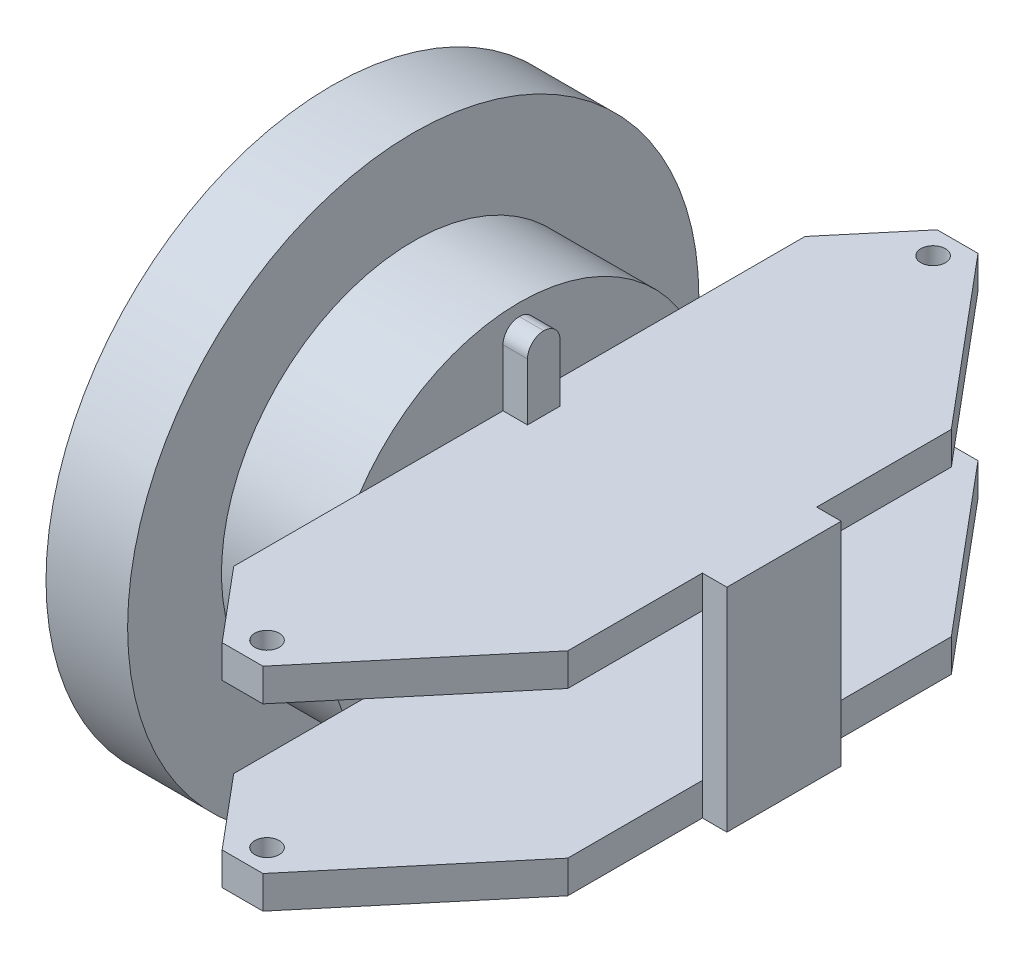
SolidWorks part; units mm, degrees
ref_plane "Front Plane" through (0, 0, 0) normal (0, 0, 1) x (1, 0, 0)
ref_plane "Top Plane" through (0, 0, 0) normal (0, 1, 0) x (1, 0, 0)
ref_plane "Right Plane" through (0, 0, 0) normal (1, 0, 0) x (0, 0, -1)
sketch "Sketch1" plane through (0, 0, 0) normal (1, 0, 0) x (0, 0, -1)
  circle A0 centre (0, 0) radius 35
  dimension "D1" = 70
extrude "Boss-Extrude1" add sketch "Sketch1" along normal blind 10
sketch "Sketch2" plane through (10, 0, 0) normal (1, 0, 0) x (0, 0, -1)
  circle A0 centre (0, 0) radius 23.5
  dimension "D1" = 47
extrude "Boss-Extrude2" add sketch "Sketch2" along normal blind 13
ref_plane "Plane1" through (0, 13, 0) normal (0, 1, 0) x (1, 0, 0)
sketch "Sketch3" plane through (0, 13, 0) normal (0, 1, 0) x (1, 0, 0)
  line L1 (23, 0) -> (23, -35)
  line L2 (23, -23.5) -> (23, 23.5) construction
  dimension "D1" = 35
sketch "Sketch5" plane through (0, 13, 0) normal (0, 1, 0) x (1, 0, 0)
  line L0 (23, 35) -> (23, -35)
  line L1 (23, -23.5) -> (23, 23.5) construction
  line L2 (23, -35) -> (30.3921, -43.8095)
  line L3 (30.3921, -43.8095) -> (35.3921, -43.8095)
  line L4 (35.3921, -43.8095) -> (52.4338, -23.5)
  line L5 (35.3921, -43.8095) -> (50.1849, -43.8095) construction
  line L6 (23, -23.5) -> (59.4908, -23.5) construction
  line L7 (52.4338, -23.5) -> (52.4338, 23.5)
  line L8 (23, 0) -> (54.5738, 0) construction
  line L9 (23, 35) -> (30.3921, 43.8095)
  line L10 (35.3921, 43.8095) -> (50.1849, 43.8095) construction
  line L11 (35.3921, 43.8095) -> (52.4338, 23.5)
  line L12 (30.3921, 43.8095) -> (35.3921, 43.8095)
  line L13 (10, -23.5) -> (23, -23.5) construction
  point P15 (52.4338, 0)
  dimension "D1" = 35
  dimension "D2" = 11.5
  dimension "D3" = 40
  dimension "D4" = 5
  dimension "D5" = 50
extrude "Boss-Extrude3" add sketch "Sketch5" against normal blind 4
sketch "Sketch7" plane through (0, 9, 0) normal (0, -1, 0) x (-1, 0, 0)
  line L0 (-30.3921, -43.8095) -> (-35.3921, -43.8095) construction
  circle A0 centre (32.8921, -46.8095) radius 1.5
  dimension "D1" = 3
  dimension "D2" = 3
sketch "Sketch8" plane through (23, 0, 0) normal (1, 0, 0) x (0, 0, -1)
  line L0 (0, 9) -> (0, 23.5) construction
  line L1 (-23.5, 9) -> (23.5, 9) construction
  line L2 (-1.3659, 9) -> (-1.3659, 18)
  line L3 (-21.7083, 9) -> (21.7083, 9) construction
  line L4 (-1.3659, 18) -> (1.2357, 18)
  line L5 (1.2357, 18) -> (1.2357, 9)
  line L6 (1.2357, 9) -> (-1.3659, 9)
  arc A0 (-21.7083, 9) -> (21.7083, 9) centre (0, 0) ccw construction
  dimension "D1" = 9
sketch "Sketch9" plane through (23, 0, 0) normal (1, 0, 0) x (0, 0, -1)
  line L0 (0, 13) -> (0, 23.5) construction
  line L1 (19.5768, 13) -> (-19.5768, 13) construction
  line L2 (-2, 13) -> (-2, 22)
  line L3 (-2, 22) -> (2, 22)
  line L4 (2, 22) -> (2, 13)
  line L5 (2, 13) -> (-2, 13)
  arc A0 (19.5768, 13) -> (-19.5768, 13) centre (0, 0) ccw construction
  dimension "D1" = 9
  dimension "D2" = 2
  dimension "D3" = 2
sketch "Sketch11" plane through (0, 13, 0) normal (0, 1, 0) x (1, 0, 0)
  line L0 (30.3921, -43.8095) -> (35.3921, -43.8095) construction
  circle A0 centre (32.8921, -40.8095) radius 1.5
  dimension "D1" = 3
  dimension "D2" = 3
extrude "Cut-Extrude2" cut sketch "Sketch11" against normal blind 4
mirror "Mirror4" about plane through (0, 0, 0) normal (0, 0, 1) of "Cut-Extrude2"
mirror "Mirror5" about plane through (0, 0, 0) normal (0, 1, 0) of "Boss-Extrude3"
mirror "Mirror6" about plane through (0, 0, 0) normal (0, 1, 0) of "Mirror4"
sketch "Sketch12" plane through (23, 0, 0) normal (1, 0, 0) x (0, 0, -1)
  line L0 (0, 13) -> (0, 23.5) construction
  line L1 (-23.5, 13) -> (23.5, 13) construction
  line L2 (-2, 13) -> (-2, 22)
  line L3 (19.5768, 13) -> (-19.5768, 13) construction
  line L4 (-2, 22) -> (2, 22)
  line L5 (2, 22) -> (2, 13)
  line L6 (2, 13) -> (-2, 13)
  arc A0 (19.5768, 13) -> (-19.5768, 13) centre (0, 0) ccw construction
  dimension "D1" = 9
  dimension "D2" = 2
  dimension "D3" = 2
extrude "Boss-Extrude4" add sketch "Sketch12" along normal blind 3
fillet "Fillet1" radius 2 2 edges at (24.5, 22, 2) (24.5, 22, -2)
mirror "Mirror7" about plane through (0, 0, 0) normal (0, 1, 0) of "Fillet1", "Boss-Extrude4"
sketch "Sketch13" plane through (52.4338, 0, 0) normal (1, 0, 0) x (0, 0, -1)
  line L1 (-7, 13) -> (7, 13)
  line L2 (-7, 13) -> (-7, -13)
  line L3 (-7, -13) -> (7, -13)
  line L4 (7, 13) -> (7, -13)
  line L5 (-7, 13) -> (7, -13) construction
  line L6 (-7, -13) -> (7, 13) construction
  point P0 (0, 0)
  dimension "D1" = 14
  dimension "D2" = 26
extrude "Boss-Extrude5" add sketch "Sketch13" along normal blind 3
sketch "Sketch14" plane through (0, 0, 0) normal (-1, 0, 0) x (0, 0, 1)
  circle A0 centre (0, 0) radius 10
  dimension "D1" = 20
extrude "Cut-Extrude3" cut sketch "Sketch14" against normal blind 10
sketch "Sketch15" plane through (0, 0, 0) normal (0, 0, 1) x (1, 0, 0)
  line L0 (0, 0) -> (193.5346, 0) construction
